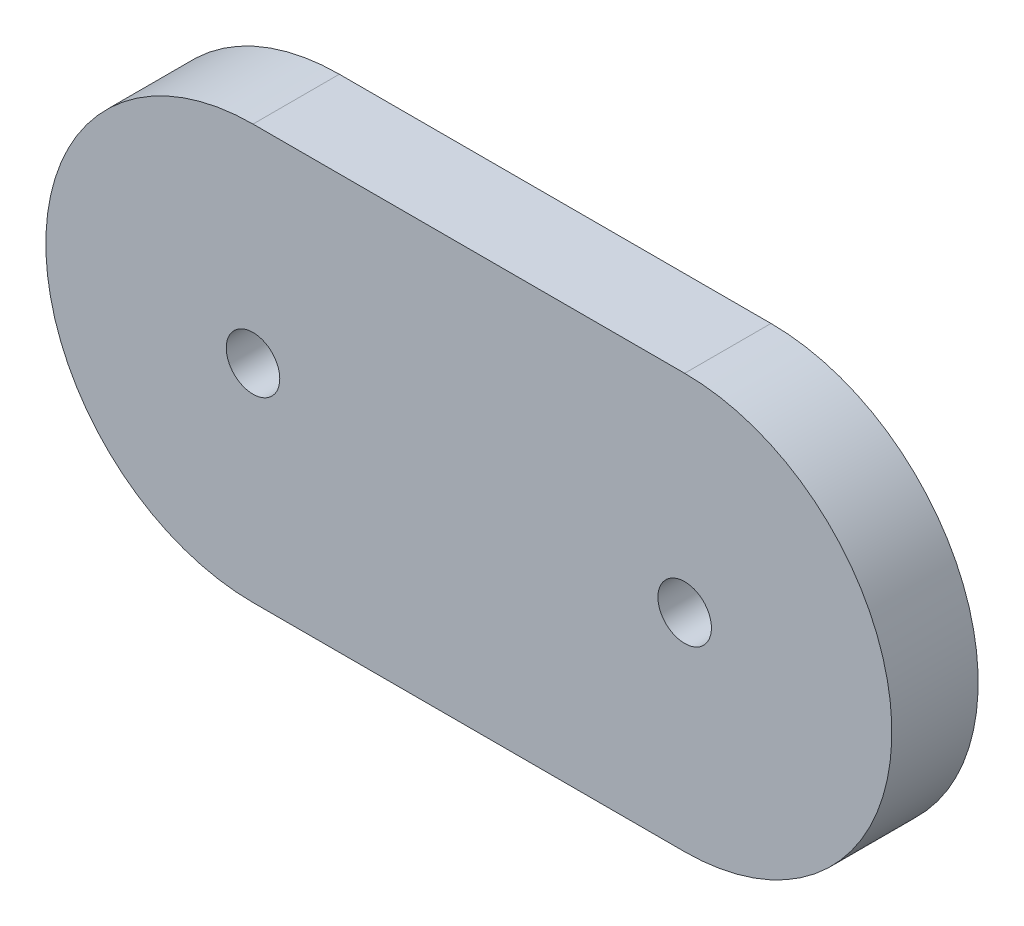
SolidWorks part; units mm, degrees
ref_plane "前视基准面" through (0, 0, 0) normal (0, 0, 1) x (1, 0, 0)
ref_plane "上视基准面" through (0, 0, 0) normal (0, 1, 0) x (1, 0, 0)
ref_plane "右视基准面" through (0, 0, 0) normal (1, 0, 0) x (0, 0, -1)
sketch "草图1" plane through (0, 0, 0) normal (0, 0, 1) x (1, 0, 0)
  line L0 (0, 0) -> (25, 0) construction
  line L1 (0, 12) -> (25, 12)
  line L2 (0, -12) -> (25, -12)
  arc A0 (0, 12) -> (0, -12) centre (0, 0) ccw
  arc A1 (25, -12) -> (25, 12) centre (25, 0) ccw
  point P3 (12.5, 0)
  dimension "D1" = 12
  dimension "D2" = 25
extrude "凸台-拉伸1" add sketch "草图1" along normal blind 5
sketch "草图2" plane through (0, 0, 0) normal (0, 0, -1) x (-1, 0, 0)
  circle A0 centre (0, 0) radius 1.55
  circle A1 centre (-25, 0) radius 1.55
  dimension "D1" = 3.1
  dimension "D2" = 3.1
extrude "切除-拉伸1" cut sketch "草图2" against normal blind 12
